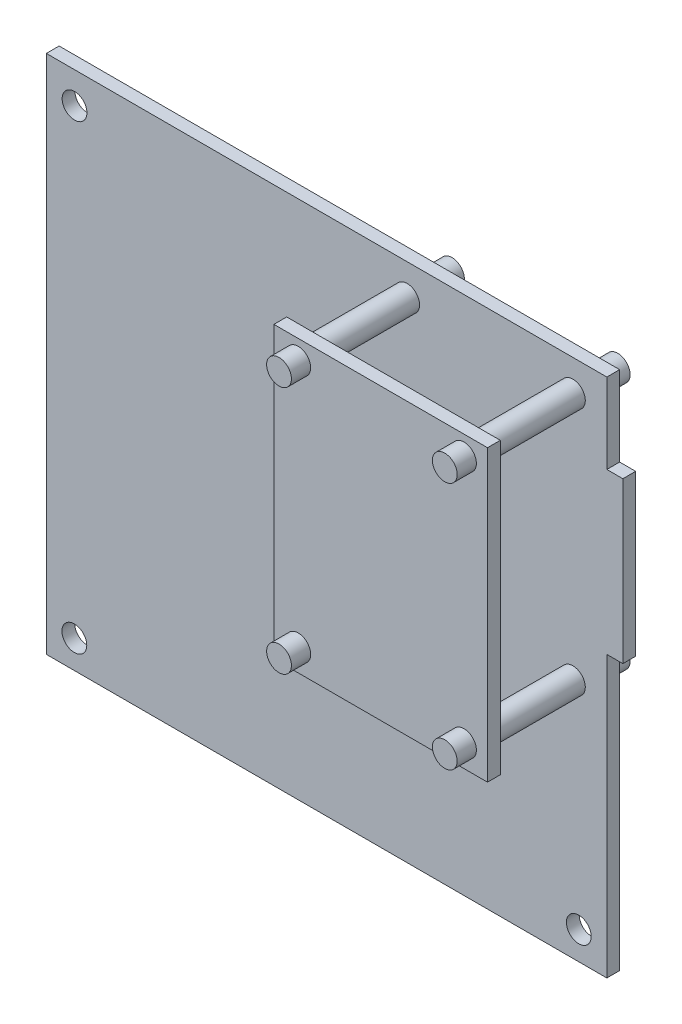
SolidWorks part; units mm, degrees
ref_plane "Front Plane" through (0, 0, 0) normal (0, 0, 1) x (1, 0, 0)
ref_plane "Top Plane" through (0, 0, 0) normal (0, 1, 0) x (1, 0, 0)
ref_plane "Right Plane" through (0, 0, 0) normal (1, 0, 0) x (0, 0, -1)
sketch "Sketch1" plane through (0, 0, 0) normal (0, 0, 1) x (1, 0, 0)
  line L0 (70, 55) -> (70, 65)
  line L1 (0, 0) -> (70, 0)
  line L2 (0, 0) -> (0, 65)
  line L3 (0, 65) -> (70, 65)
  line L4 (70, 0) -> (70, 35)
  line L5 (70, 55) -> (72, 55)
  line L7 (70, 35) -> (72, 35)
  line L8 (72, 55) -> (72, 35)
  circle A0 centre (3.523, 61.1) radius 1.55
  circle A1 centre (3.5, 3.5) radius 1.55
  circle A2 centre (66.5, 3.5) radius 1.55
  circle A3 centre (45.06, 61.1) radius 1.55
  circle A4 centre (65.76, 61.1) radius 1.55
  circle A5 centre (45.06, 30.1) radius 1.55
  circle A6 centre (65.76, 30.1) radius 1.55
  dimension "D3" = 3.1
  dimension "D4" = 3.1
  dimension "D5" = 3.1
  dimension "D12" = 3.1
  dimension "D14" = 3.1
  dimension "D15" = 3.1
  dimension "D16" = 3.1
  dimension "D1" = 70
  dimension "D2" = 65
  dimension "D6" = 3.5
  dimension "D7" = 3.5
  dimension "D8" = 3.5
  dimension "D9" = 3.5
  dimension "D10" = 3.523
  dimension "D11" = 3.9
  dimension "D13" = 3.9
  dimension "D17" = 20.7
  dimension "D18" = 20.7
  dimension "D19" = 31
  dimension "D20" = 4.24
  dimension "D21" = 4.24
  dimension "D22" = 20
  dimension "D23" = 10
  dimension "D24" = 2
extrude "Boss-Extrude1" add sketch "Sketch1" along normal blind 1.6
extrude "Boss-Extrude2" add sketch "Sketch1<3>" against normal blind 4 separate body contours A6 | A3 | A4 | A5 region at (65.76, 30.1, 0)
sketch "Sketch1<3>" plane through (0, 0, 0) normal (0, 0, 1) x (1, 0, 0) same geometry as "Sketch1"
extrude "Boss-Extrude3" add sketch "Sketch1<4>" along normal blind 17.6 contours A3 | A4 | A5 | A6 region at (45.06, 61.1, 0) region at (65.76, 61.1, 0) region at (45.06, 30.1, 0) region at (65.76, 30.1, 0)
sketch "Sketch1<4>" plane through (0, 0, 0) normal (0, 0, 1) x (1, 0, 0) same geometry as "Sketch1"
sketch "Sketch2" plane through (0, 0, 1.6) normal (0, 0, 1) x (1, 0, 0)
  line L1 (68.6953, 27.3277) -> (42.0173, 27.3277)
  line L2 (68.6953, 27.3277) -> (68.6953, 63.5033)
  line L3 (68.6953, 63.5033) -> (42.0173, 63.5033)
  line L4 (42.0173, 27.3277) -> (42.0173, 63.5033)
extrude "Boss-Extrude4" add sketch "Sketch2" along normal blind 1.6 from offset 12
